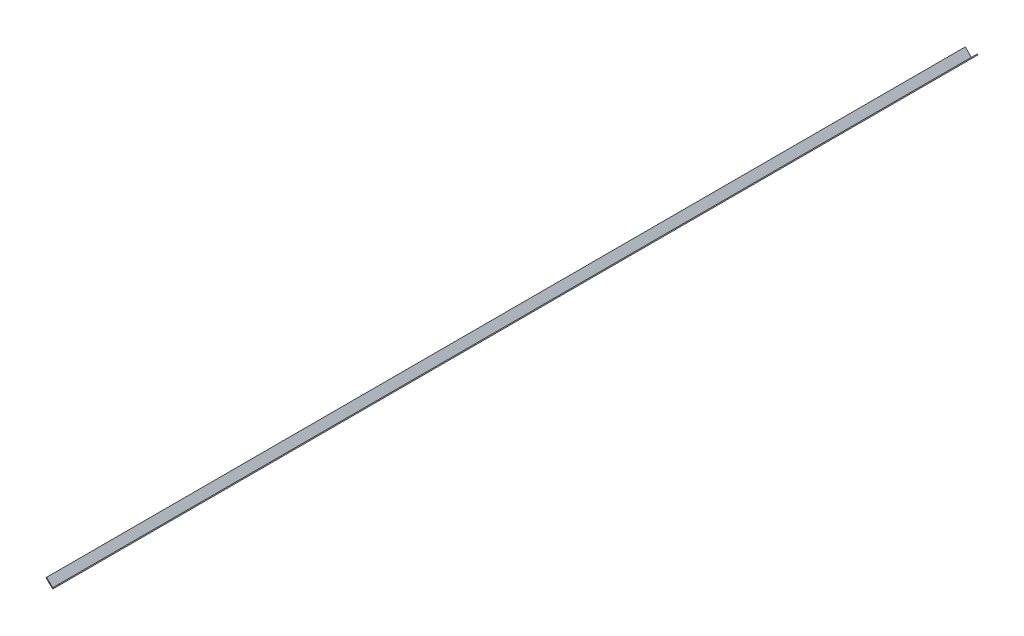
SolidWorks part; units mm, degrees
material "6061 Alloy"
ref_plane "Front Plane" through (0, 0, 0) normal (0, 0, 1) x (1, 0, 0)
ref_plane "Top Plane" through (0, 0, 0) normal (0, 1, 0) x (1, 0, 0)
ref_plane "Right Plane" through (0, 0, 0) normal (1, 0, 0) x (0, 0, -1)
sketch "Sketch1" plane through (0, 0, 0) normal (0, 0, 1) x (1, 0, 0)
  line L0 (0, 0) -> (-8.9803, 8.9803)
  line L1 (-8.9803, 8.9803) -> (-9.8783, 8.0822)
  line L2 (-9.8783, 8.0822) -> (0, -1.7961)
  line L3 (0, -1.7961) -> (9.8783, 8.0822)
  line L4 (9.8783, 8.0822) -> (8.9803, 8.9803)
  line L5 (8.9803, 8.9803) -> (0, 0)
  line L6 (-13.872, 0) -> (16.6117, 0) construction
  dimension "D1" = 1.27
  dimension "D2" = 12.7
extrude "Boss-Extrude1" add sketch "Sketch1" along normal blind 1289.05 and the other way blind 76.2
